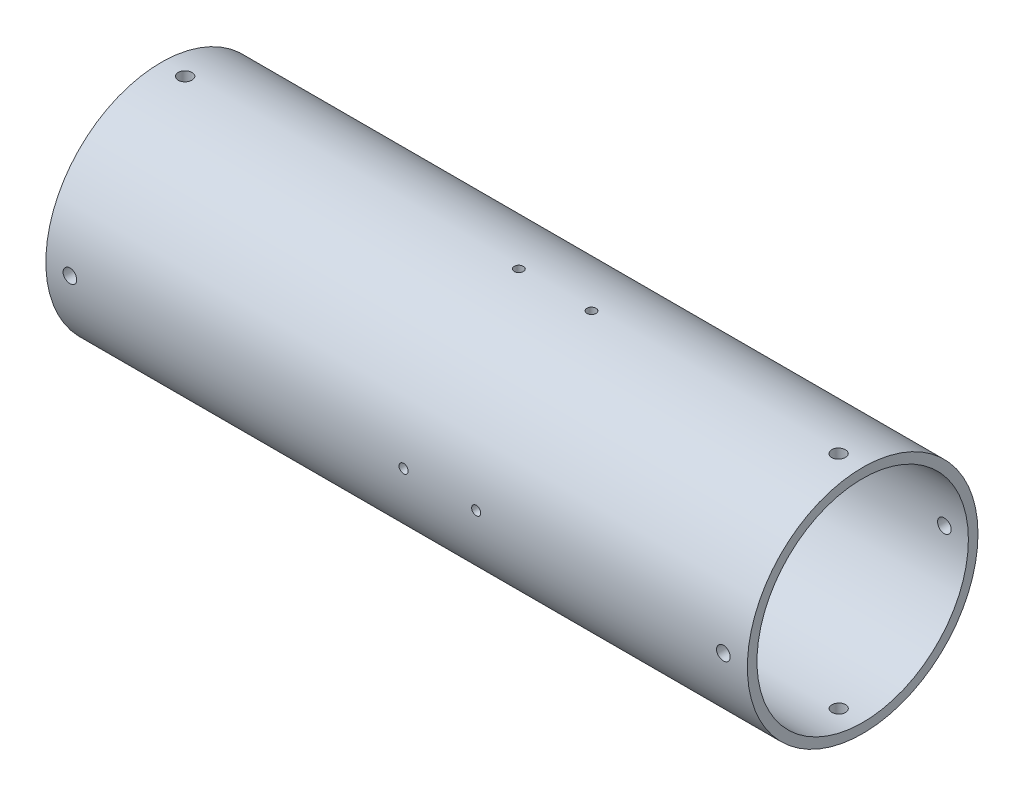
SolidWorks part; units mm, degrees
material "PVC Rigid"
ref_plane "Front Plane" through (0, 0, 0) normal (0, 0, 1) x (1, 0, 0)
ref_plane "Top Plane" through (0, 0, 0) normal (0, 1, 0) x (1, 0, 0)
ref_plane "Right Plane" through (0, 0, 0) normal (1, 0, 0) x (0, 0, -1)
sketch "Sketch2" plane through (0, 0, 0) normal (1, 0, 0) x (0, 0, -1)
  circle A0 centre (0, 0) radius 34.925
  circle A1 centre (0, 0) radius 38.1
  dimension "D1" = 69.85
  dimension "D2" = 76.2
extrude "Boss-Extrude1" add sketch "Sketch2" along normal mid plane 231.775
ref_plane "Plane1" through (0, 38.1, 0) normal (0, 1, 0) x (1, 0, 0)
ref_plane "cam plane" through (14.2875, 0, 0) normal (1, 0, 0) x (0, 0, -1)
sketch "Sketch3" plane through (0, 38.1, 0) normal (0, 1, 0) x (1, 0, 0)
  line L0 (14.2875, 0) -> (2.2875, 0) construction
  line L2 (14.2875, -41.91) -> (14.2875, 41.91) construction
  circle A0 centre (2.2875, 0) radius 1.5
  dimension "D1" = 3
  dimension "D2" = 12
extrude "Cut-Extrude1" cut sketch "Sketch3" against normal blind 4.5
pattern_circular "CirPattern1" count 3 every 90 about axis through (115.8875, 0, 0) along (-1, 0, 0) of "Cut-Extrude1" reverse direction yes
ref_plane "Plane3" through (0, -20.1899, -32.3106) normal (0, -0.5299, -0.848) x (-1, 0, 0)
sketch "Sketch5" plane through (0, -20.1899, -32.3106) normal (0, -0.5299, -0.848) x (-1, 0, 0)
  line L0 (-14.2875, 41.91) -> (-14.2875, -41.91) construction
  line L1 (9.7125, -12) -> (-8.2875, -12)
  line L2 (9.7125, -12) -> (9.7125, 12)
  line L3 (9.7125, 12) -> (-8.2875, 12)
  line L4 (-8.2875, -12) -> (-8.2875, 12)
  line L5 (9.7125, -12) -> (-8.2875, 12) construction
  line L6 (9.7125, 12) -> (-8.2875, -12) construction
  line L7 (-115.8875, 0) -> (0.7125, 0) construction
  line L8 (-115.8875, 38.1) -> (-115.8875, -38.1) construction
  point P0 (0.7125, 0)
  dimension "D1" = 18
  dimension "D2" = 24
  dimension "D3" = 15
extrude "Cut-Extrude3" cut sketch "Sketch5" against normal blind 15.5
mirror "Mirror1" about plane through (14.2875, 0, 0) normal (1, 0, 0) of "Cut-Extrude3", "CirPattern1"
ref_plane "Plane4" through (0, 0, -38.1) normal (0, 0, -1) x (-1, 0, 0)
sketch "Sketch6" plane through (0, 0, -38.1) normal (0, 0, -1) x (-1, 0, 0)
  line L0 (-14.2875, 41.91) -> (-14.2875, -41.91) construction
  line L1 (-11.2875, 8.9858) -> (0.7125, 8.9858)
  line L2 (-11.2875, 8.9858) -> (-11.2875, -8.9858)
  line L3 (-11.2875, -8.9858) -> (0.7125, -8.9858)
  line L4 (0.7125, 8.9858) -> (0.7125, -8.9858)
  line L5 (-11.2875, 8.9858) -> (0.7125, -8.9858) construction
  line L6 (-11.2875, -8.9858) -> (0.7125, 8.9858) construction
  line L7 (-8.2875, -8.9858) -> (9.7125, -8.9858) construction
  point P0 (-5.2875, 0)
  point P15 (0.7125, -8.9858)
  dimension "D1" = 17.9716
  dimension "D2" = 9
extrude "Cut-Extrude4" cut sketch "Sketch6" against normal blind 19
fillet "Fillet1" radius 5 7 edges at (20.2875, -8.0949, -35.5996) (20.2875, -28.4481, -22.8815) (38.2875, -28.4481, -22.8815) (-9.7125, -8.0949, -35.5996) (8.2875, -28.4481, -22.8815) (-9.7125, -28.4481, -22.8815) (38.2875, -8.0949, -35.5996)
fillet "Fillet2" radius 1.5 5 edges at (11.2875, 8.9858, -35.3872) (-0.7125, 8.9858, -35.3872) (11.2875, -8.9858, -35.3872) (-0.7125, -8.0949, -35.5996) (8.2875, -8.9858, -35.3872)
sketch "Sketch9" plane through (0, 0, 0) normal (0, 0, 1) x (1, 0, 0)
  line L0 (115.8875, -38.1) -> (115.8875, 38.1) construction
  point P0 (107.95, 0)
  dimension "D1" = 7.9375
hole_wizard "#8 Clearance Hole1" positions "3DSketch1" profile "Sketch10" hole size "#8" standard "ANSI Inch" end condition up to next
sketch3d "3DSketch1"
  point P0 (107.95, 0, 38.1)
sketch "Sketch10" plane through (107.95, 0, 38.1) normal (1, 0, 0) x (0, -1, 0)
  line L0 (0, 0) -> (0, 3.175)
  line L1 (0, 3.175) -> (2.2479, 3.175)
  line L2 (2.2479, 3.175) -> (2.2479, 0)
  line L5 (2.2479, 0) -> (0, 0)
  line L11 (0, -6.35) -> (0, 107.95) construction
  dimension "Thru Hole Dia." = 4.4958
  dimension "Thru Hole Depth" = 3.175
pattern_circular "CirPattern2" count 4 over 360 about axis through (115.8875, 0, 0) along (-1, 0, 0) of "#8 Clearance Hole1"
mirror "Mirror2" about plane through (0, 0, 0) normal (1, 0, 0) of "CirPattern2"
